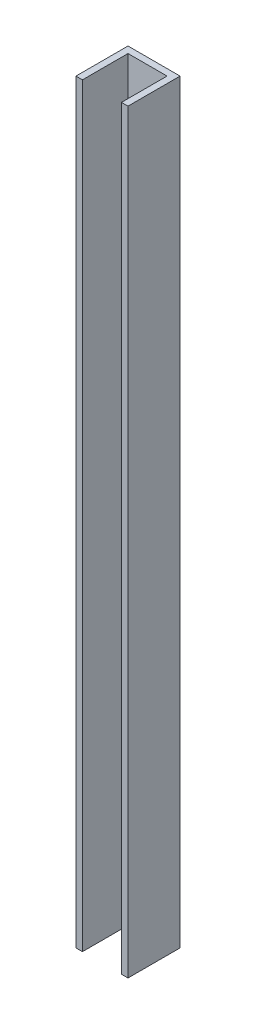
SolidWorks part; units mm, degrees
material "Plain Carbon Steel"
ref_plane "Front Plane" through (0, 0, 0) normal (0, 0, 1) x (1, 0, 0)
ref_plane "Top Plane" through (0, 0, 0) normal (0, 1, 0) x (1, 0, 0)
ref_plane "Right Plane" through (0, 0, 0) normal (1, 0, 0) x (0, 0, -1)
sketch "Sketch1" plane through (0, 0, 0) normal (0, 1, 0) x (1, 0, 0)
  line L0 (0, 0) -> (3.175, 0)
  line L1 (0, 0) -> (0, 25.4)
  line L2 (0, 25.4) -> (25.4, 25.4)
  line L3 (25.4, 25.4) -> (25.4, 0)
  line L4 (25.4, 0) -> (22.225, 0)
  line L5 (22.225, 0) -> (22.225, 22.225)
  line L6 (22.225, 22.225) -> (3.175, 22.225)
  line L7 (3.175, 22.225) -> (3.175, 0)
extrude "Boss-Extrude1" add sketch "Sketch1" along normal blind 368.3 contours L2 L3 L4 L5 L6 L7 L0 L1
